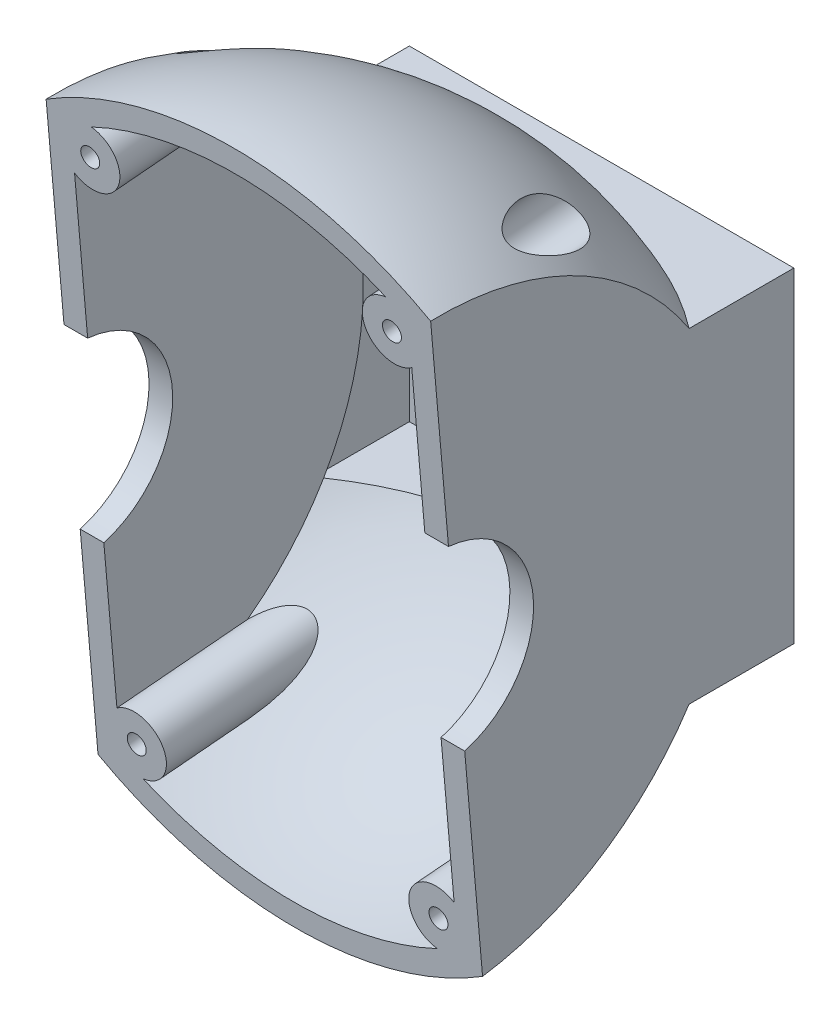
SolidWorks part; units mm, degrees
ref_plane "Front Plane" through (0, 0, 0) normal (0, 0, 1) x (1, 0, 0)
ref_plane "Top Plane" through (0, 0, 0) normal (0, 1, 0) x (1, 0, 0)
ref_plane "Right Plane" through (0, 0, 0) normal (1, 0, 0) x (0, 0, -1)
sketch "Sketch1" plane through (0, 0, 0) normal (0, 0, 1) x (1, 0, 0)
  line L0 (-32.5, 0) -> (-32.5, 50.4356)
  line L1 (32.5, 50.4356) -> (32.5, 0)
  line L2 (-32.5, 0) -> (32.5, 0) construction
  line L3 (-28.5, 0) -> (-28.5, 48.2053)
  line L4 (28.5, 48.2053) -> (28.5, 0)
  arc A0 (-32.5, 50.4356) -> (32.5, 50.4356) centre (0, 0) cw
  arc A1 (-28.5, 48.2053) -> (28.5, 48.2053) centre (0, 0) cw
  point P4 (0, 0)
  dimension "D1" = 60
  dimension "D2" = 65
  dimension "D3" = 4
revolve "Revolve1" add sketch "Sketch1" angle 360 about L2 region at (-31.6154, 25.2178, 0)
ref_plane "Plane3" through (0, 0, -60) normal (0, 0, -1) x (-1, 0, 0)
sketch "Sketch13" plane through (0, 0, -60) normal (0, 0, -1) x (-1, 0, 0)
  line L0 (-32.5, 50.4356) -> (-32.5, -50.4356) construction
  line L1 (-32.5, 27.5) -> (32.5, 27.5)
  line L2 (-32.5, 27.5) -> (-32.5, -27.5)
  line L3 (-32.5, -27.5) -> (32.5, -27.5)
  line L4 (32.5, 27.5) -> (32.5, -27.5)
  line L5 (32.5, -50.4356) -> (32.5, 50.4356) construction
  point P8 (-32.5, 0)
  dimension "D1" = 55
extrude "Boss-Extrude7" add sketch "Sketch13" against normal up to next
sketch "Sketch3" plane through (32.5, 0, 0) normal (1, 0, 0) x (0, 0, -1)
  circle A0 centre (0, 0) radius 10
  dimension "D1" = 20
extrude "Cut-Extrude1" cut sketch "Sketch3" against normal up to next
sketch "Sketch4" plane through (32.5, 0, 0) normal (1, 0, 0) x (0, 0, -1)
  circle A0 centre (0, 0) radius 10 construction
  circle A1 centre (0, 0) radius 10
  circle A2 centre (0, 0) radius 12
  dimension "D1" = 2
extrude "Boss-Extrude2" add sketch "Sketch4" along normal blind 1
ref_plane "Plane4" through (0, 0, -57) normal (0, 0, -1) x (-1, 0, 0)
sketch "Sketch15" plane through (0, 0, -57) normal (0, 0, -1) x (-1, 0, 0)
  line L8 (-29.5, 24.5) -> (-29.5, -24.5)
  line L9 (-29.5, -24.5) -> (29.5, -24.5)
  line L10 (29.5, -24.5) -> (29.5, 24.5)
  line L11 (29.5, 24.5) -> (-29.5, 24.5)
  line L12 (-29.5, 24.5) -> (-29.5, -24.5)
  line L13 (-29.5, -24.5) -> (29.5, -24.5)
  line L14 (29.5, -24.5) -> (29.5, 24.5)
  line L15 (29.5, 24.5) -> (-29.5, 24.5)
  dimension "D1" = 3
extrude "Cut-Extrude4" cut sketch "Sketch15" against normal up to surface (16.1895 mm away) up to face at (28.5, -48.2053, 0)
sketch "Sketch16" plane through (-32.5, 0, 0) normal (-1, 0, 0) x (0, 0, 1)
  circle A0 centre (0, 0) radius 7.5
  dimension "D1" = 15
extrude "Cut-Extrude5" cut sketch "Sketch16" against normal up to next
sketch "Sketch18" plane through (-32.5, 0, 0) normal (-1, 0, 0) x (0, 0, 1)
  circle A0 centre (0, 0) radius 7.5 construction
  circle A1 centre (0, 0) radius 7.5
  circle A2 centre (0, 0) radius 9.5
  dimension "D1" = 2
extrude "Boss-Extrude8" add sketch "Sketch18" along normal blind 10
sketch "Sketch19" plane through (-32.5, 0, 0) normal (-1, 0, 0) x (0, 0, 1)
  circle A0 centre (0, 0) radius 11.5
  circle A1 centre (0, 0) radius 9.5 construction
  circle A3 centre (0, 0) radius 9.5
  dimension "D1" = 2
extrude "Boss-Extrude9" add sketch "Sketch19" along normal blind 1
sketch "Sketch10" plane through (0, 0, 0) normal (0, 0, 1) x (1, 0, 0)
  line L0 (28.5, 48.2053) -> (28.5, -48.2053) construction
  line L1 (13.5, -2.6) -> (9.5, -2.6)
  line L2 (13.5, -2.6) -> (13.5, -32.6)
  line L3 (13.5, -32.6) -> (9.5, -32.6)
  line L4 (9.5, -2.6) -> (9.5, -32.6)
  dimension "D1" = 4
  dimension "D2" = 15
  dimension "D3" = 30
  dimension "D4" = 2.6
extrude "Boss-Extrude4" [suppressed] add sketch "Sketch10" along normal up to next and the other way blind 7.5
sketch "Sketch11" [suppressed] plane through (12, 0, 0) normal (-1, 0, 0) x (0, 0, 1)
  line L1 (46.1, -17.35) -> (-2.5, -17.35) construction
  line L2 (46.1, -17.35) -> (46.1, -7.6) construction
  line L3 (46.1, -7.6) -> (-2.5, -7.6) construction
  line L4 (-2.5, -17.35) -> (-2.5, -7.6) construction
  line L5 (-7.5, -2.6) -> (59.7515, -2.6) construction
  line L6 (-7.5, -2.6) -> (-7.5, -32.6) construction
  line L7 (1.55, -2.6) -> (42.05, -2.6)
  line L8 (42.05, -2.6) -> (42.05, -23.35)
  line L9 (42.05, -23.35) -> (1.55, -23.35)
  line L10 (1.55, -23.35) -> (1.55, -2.6)
  line L11 (21.8, -17.35) -> (21.8, -18.0186) construction
  circle A0 centre (46.1, -17.35) radius 2
  circle A1 centre (46.1, -7.6) radius 2
  circle A2 centre (-2.5, -7.6) radius 2
  circle A3 centre (-2.5, -17.35) radius 2
  point P8 (21.8, -23.35)
  dimension "D3" = 4
  dimension "D1" = 48.6
  dimension "D2" = 9.75
  dimension "D6" = 40.5
  dimension "D7" = 6
  dimension "D4" = 5
  dimension "D5" = 5
extrude "Cut-Extrude3" [suppressed] cut sketch "Sketch11" against normal up to next
sketch "Sketch5" plane through (0, 0, 0) normal (1, 0, 0) x (0, 0, -1)
  line L0 (4.3583, -15.395) -> (8.2608, -60)
  line L1 (60, 60) -> (-2.2379, 60)
  line L2 (60, 60) -> (60, -60)
  line L3 (60, -60) -> (8.2608, -60)
  line L4 (-2.2379, 60) -> (1.6188, 15.9179)
  circle A0 centre (0, 0) radius 60 construction
  circle A1 centre (0, 0) radius 60 construction
  circle A2 centre (0, 0) radius 12 construction
  circle A3 centre (0, 0) radius 12 construction
  arc A4 (4.3583, -15.395) -> (1.6188, 15.9179) centre (0, 0) ccw
  circle A5 centre (0, 0) radius 16 construction
  dimension "D1" = 3
  dimension "D3" = 95
  dimension "D2" = 4
extrude "Cut-Extrude2" cut sketch "Sketch5" against normal through all both and the other way through all flip side to cut
sketch "Sketch24" plane through (0, 0.2615, -2.9886) normal (0, -0.0872, 0.9962) x (1, 0, 0)
  line L0 (-25.5, 45.1118) -> (-25.5, -45.1118) construction
  line L1 (-28.5, 48.1118) -> (28.5, 48.1118) construction
  line L2 (-28.5, 48.1118) -> (-28.5, -48.1118) construction
  line L3 (-28.5, -48.1118) -> (28.5, -48.1118) construction
  line L4 (28.5, 48.1118) -> (28.5, -48.1118) construction
  line L5 (-25.5, -45.1118) -> (25.5, -45.1118) construction
  line L6 (25.5, 45.1118) -> (25.5, -45.1118) construction
  line L7 (-25.5, 45.1118) -> (25.5, 45.1118) construction
  circle A0 centre (-25.5, 45.1118) radius 5
  circle A1 centre (25.5, 45.1118) radius 5
  circle A2 centre (-25.5, -45.1118) radius 5
  circle A3 centre (25.5, -45.1118) radius 5
  dimension "D2" = 10
  dimension "D1" = 3
extrude "Boss-Extrude11" add sketch "Sketch24" against normal up to surface (26.6106 mm away) up to face at (0, 41.1956, -23.8069)
ref_plane "Plane6" through (0, 5.2293, -59.7717) normal (0, 0.0872, -0.9962) x (-1, 0, 0)
sketch "Sketch25" plane through (0, 5.2293, -59.7717) normal (0, 0.0872, -0.9962) x (-1, 0, 0)
  arc A0 (28.5, -41.1118) -> (24.8905, -50.0746) centre (25.5, -45.1118) ccw construction
  arc A1 (-24.8905, -50.0746) -> (-28.5, -41.1118) centre (-25.5, -45.1118) ccw construction
  arc A2 (-28.5, 41.1118) -> (-24.8905, 50.0746) centre (-25.5, 45.1118) ccw construction
  arc A3 (24.8905, 50.0746) -> (28.5, 41.1118) centre (25.5, 45.1118) ccw construction
  arc A4 (28.5, -41.1118) -> (24.8905, -50.0746) centre (25.5, -45.1118) ccw construction
  arc A5 (-24.8905, -50.0746) -> (-28.5, -41.1118) centre (-25.5, -45.1118) ccw construction
  arc A6 (-28.5, 41.1118) -> (-24.8905, 50.0746) centre (-25.5, 45.1118) ccw construction
  arc A7 (24.8905, 50.0746) -> (28.5, 41.1118) centre (25.5, 45.1118) ccw construction
  circle A8 centre (-25.5, 45.1118) radius 4.5
  circle A9 centre (25.5, 45.1118) radius 4.5
  circle A10 centre (-25.5, -45.1118) radius 4.5
  circle A11 centre (25.5, -45.1118) radius 4.5
  dimension "D1" = 9
extrude "Cut-Extrude7" cut sketch "Sketch25" against normal offset from surface (55 mm away) 2 up to face at (0, 35.7913, 0.1199)
hole_wizard "M3 Clearance Hole2" positions "Sketch26" profile "Sketch27" hole size "M3" standard "ANSI Metric" end condition through all
sketch "Sketch26" plane through (0, 5.2293, -59.7717) normal (0, 0.0872, -0.9962) x (-1, 0, 0)
  point P0 (-25.5, 45.1118)
  point P3 (25.5, 45.1118)
  point P6 (25.5, -45.1118)
  point P9 (-25.5, -45.1118)
sketch "Sketch27" plane through (25.5, 50.1695, -55.8399) normal (1, 0, 0) x (0, 0.9962, 0.0872)
  line L0 (0, 0) -> (0, 67.4059)
  line L1 (0, 67.4059) -> (1.6, 67.4059)
  line L2 (1.6, 67.4059) -> (1.6, 0)
  line L5 (1.6, 0) -> (0, 0)
  line L11 (0, -6.35) -> (0, 107.95) construction
  dimension "Thru Hole Dia." = 3.2
  dimension "Thru Hole Depth" = 67.4059
sketch "Sketch28" plane through (0, 0, -60) normal (0, 0, -1) x (-1, 0, 0)
  line L4 (-26.5, -21.5) -> (26.5, -21.5)
  line L5 (-26.5, -21.5) -> (26.5, -21.5)
  line L8 (-26.5, 21.5) -> (-26.5, -21.5)
  line L10 (26.5, -21.5) -> (26.5, 21.5)
  line L11 (26.5, 21.5) -> (-26.5, 21.5)
  line L12 (-26.5, 21.5) -> (-26.5, -21.5)
  line L14 (26.5, -21.5) -> (26.5, 21.5)
  line L15 (26.5, 21.5) -> (-26.5, 21.5)
  dimension "D1" = 6
extrude "TEMPORARY CUT" cut sketch "Sketch28" against normal up to next (3 mm away)
equation "\"D5@Sketch11\"=\"D4@Sketch11\""
